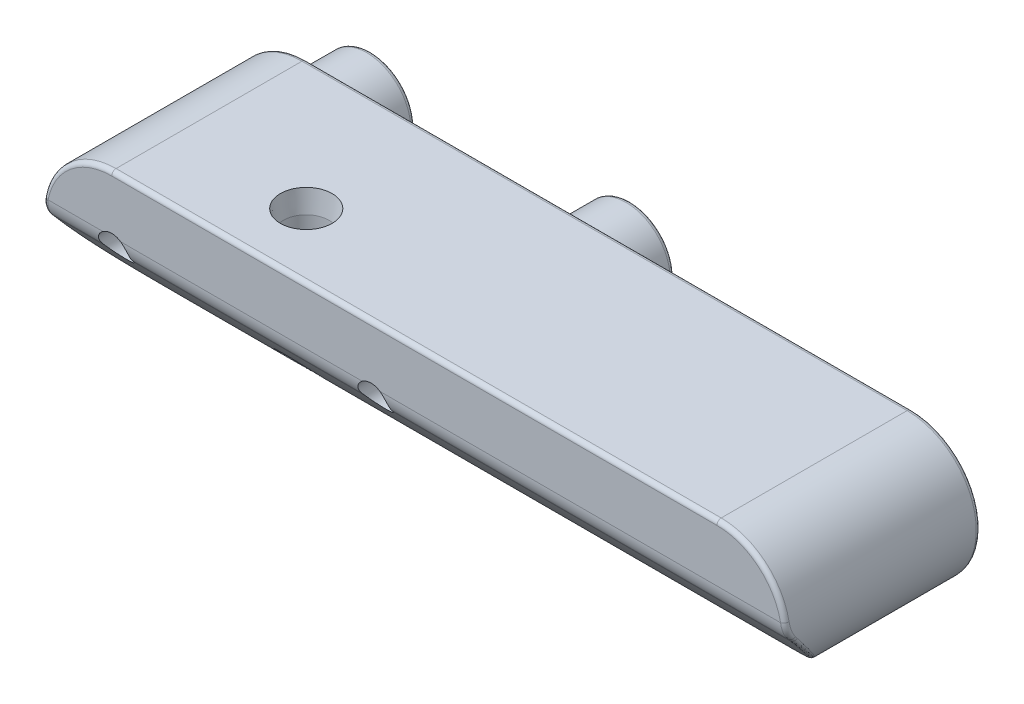
SolidWorks part; units mm, degrees
other "Markup1"
sketch "Sketch17" plane through (63.0877, 8, -7.5) normal (0.0924, 0.1207, -0.9884) x (-0.9911, 0.1065, -0.0797)
ref_plane "Front Plane" through (0, 0, 0) normal (0, 0, 1) x (1, 0, 0)
ref_plane "Top Plane" through (0, 0, 0) normal (0, 1, 0) x (1, 0, 0)
ref_plane "Right Plane" through (0, 0, 0) normal (1, 0, 0) x (0, 0, -1)
sketch "Sketch1" plane through (0, 0, 0) normal (0, 0, 1) x (1, 0, 0)
  line L0 (0, 0) -> (-15, 0) construction
  line L1 (15, 0) -> (-15, 0) construction
  line L2 (15, -8) -> (-15, -8)
  line L3 (15, 8) -> (-15, 8)
  line L4 (15, 0) -> (55, 0) construction
  line L5 (15, 8) -> (55, 8)
  line L6 (15, -8) -> (55, -8)
  arc A1 (15, -8) -> (15, 8) centre (15, 0) ccw
  arc A2 (-15, 8) -> (-15, -8) centre (-15, 0) ccw
  arc A3 (15, 8) -> (15, -8) centre (15, 0) ccw
  arc A4 (55, -8) -> (55, 8) centre (55, 0) ccw
  point P4 (0, 0)
  point P11 (35, 0)
  dimension "D2" = 8
  dimension "D1" = 15
  dimension "D3" = 40
extrude "Boss-Extrude1" add sketch "Sketch1" along normal blind 22.5 contours A3 L3 A2 L2 | A1 A3 | L6 A4 L5 A1 region at (41.2832, 0, 0) region at (15, 0, 0) region at (-6.2832, 0, 0)
sketch "Sketch2" plane through (0, 0, 0) normal (0, 0, -1) x (-1, 0, 0)
  line L0 (0, 0) -> (15, 0) construction
  line L1 (-15, 0) -> (0, 0) construction
  circle A0 centre (15, 0) radius 5.1
  circle A1 centre (-15, 0) radius 5.1
  dimension "D2" = 10.2
  dimension "D1" = 15
extrude "Boss-Extrude2" add sketch "Sketch2" along normal blind 7.5
fillet "Fillet1" radius 2 2 edges at (-9.9, 0, 0) (20.1, 0, 0)
sketch "Sketch4" plane through (0, 0, -7.5) normal (0, 0, -1) x (-1, 0, 0)
  circle A0 centre (-15, 0) radius 1.76
  circle A1 centre (15, 0) radius 1.76
  circle A2 centre (-15, 0) radius 5.1 construction
  circle A3 centre (15, 0) radius 5.1 construction
  point P0 (-15, 0)
  point P1 (15, 0)
  dimension "D1" = 3.52
sketch "Sketch11" plane through (0, 0, 0) normal (1, 0, 0) x (0, 0, -1)
  line L1 (-22.5, 0.3423) -> (-15.5, -8)
  line L2 (-22.5, -8) -> (0, -8) construction
  line L3 (-22.5, 8) -> (-22.5, -8) construction
  line L4 (-22.5, 0.3423) -> (-22.5, -8)
  line L5 (-22.5, -8) -> (-15.5, -8)
  dimension "D1" = 50
  dimension "D2" = 7
extrude "Cut-Extrude2" cut sketch "Sketch11" against normal through all both and the other way through all
fillet "Fillet2" radius 3 1 edges at (20, 0.3423, 22.5) tangent propagation no
sketch "Sketch15" plane through (0, 0, 0) normal (0, 0, -1) x (-1, 0, 0)
  line L0 (-55, -8) -> (15, -8) construction
  line L1 (-30, -8) -> (-10, -8)
  line L2 (-30, -8) -> (-30, -18)
  line L3 (-30, -18) -> (-10, -18)
  line L4 (-10, -8) -> (-10, -18)
  line L5 (-30, -18) -> (-55, -8)
  line L6 (-10, -18) -> (15, -8)
  line L7 (15, -8) -> (-10, -8)
  line L8 (-55, -8) -> (-30, -8)
  line M9 (-55, -8) -> (15, -8)
  arc M10 (15, -8) -> (15, 8) centre (15, 0) ccw
  arc M12 (-55, 8) -> (-55, -8) centre (-55, 0) ccw
  dimension "D1" = 10
  dimension "D2" = 25
  dimension "D3" = 25
extrude "Boss-Extrude3" add sketch "Sketch15" against normal up to vertex (15.5 mm away) contours L2 M12 | L4 L2 L3 M9 | L4 M10 region at (20, -13, 0) region at (38.3333, -11.3333, 0) region at (1.6667, -11.3333, 0) up to point (-15, -8, 15.5)
sketch "Sketch12" plane through (0, 8, 0) normal (0, 1, 0) x (1, 0, 0)
  line L1 (0, 0) -> (0, -15) construction
  line L3 (55, -22.5) -> (-15, -22.5) construction
  circle A0 centre (0, -15) radius 2.6416
  dimension "D1" = 5.2832
  dimension "D2" = 7.5
extrude "Cut-Extrude3" cut sketch "Sketch12" against normal through all both contours A0
sketch "Sketch16" plane through (0, 0, 0) normal (1, 0, 0) x (0, 0, -1)
  line L0 (-15.5, -8) -> (-4, -18)
  line L2 (-4, -18) -> (-15.5, -18)
  line L3 (-15.5, -18) -> (-15.5, -8)
  line L4 (0, -18) -> (0, -8) construction
  dimension "D1" = 4
extrude "Cut-Extrude4" cut sketch "Sketch16" against normal through all both and the other way through all
fillet "Fillet3" radius 20 4 edges at (10, -18, 2) (30, -18, 2) (-15, -8, 7.75) (55, -8, 7.75)
fillet "Fillet4" radius 120 2 edges at (-9.1841, -8, 15.5) (29.1841, -8, 15.5)
fillet "Fillet5" radius 2 1 edges at (20, -18, 0) tangent propagation no
fillet "Fillet6" radius 0.5 31 edges at (29.7779, -17.6679, 0.8963) (34.2806, -16.2878, 0.0208) (10.2221, -17.6679, 0.8963) (5.7194, -16.2878, 0.0208) (3.4504, -15.3802, 7.0128) (10.0695, -17.6391, 4.415) (20, -18, 4) (29.9305, -17.6391, 4.415) (36.5496, -15.3802, 7.0128) (45.9145, -11.6342, 11.2277) (60.2308, -6.053, 16.8618) (62.9749, -0.6335, 21.6812) (62.9846, 0.4959, 22.3495) (60.1248, 6.143, 22.5) (20, 8, 22.5) (-20.1248, 6.143, 22.5) (-22.993, 0.3357, 22.2917) (-22.9749, -0.6335, 21.6812) (-20.3868, -5.9146, 16.9924) (54.4449, -8.3324, 0) (62.9683, 0.711, 0) (20, 8, 0) (-22.9683, 0.711, 0) (-14.4449, -8.3324, 0) (-3.7649, -12.494, 0) (43.7649, -12.494, 0) (-20.1, 0, -7.5) (9.9, 0, -7.5) (-5.9145, -11.6342, 11.2277)
extrude "Cut-Extrude5" cut sketch "Sketch4" against normal through all both
chamfer "Chamfer2" distance 2.5 angle 8 1 edges at (-2.6416, 8, 15) first distance on face at (-2.6416, 8, 15)
